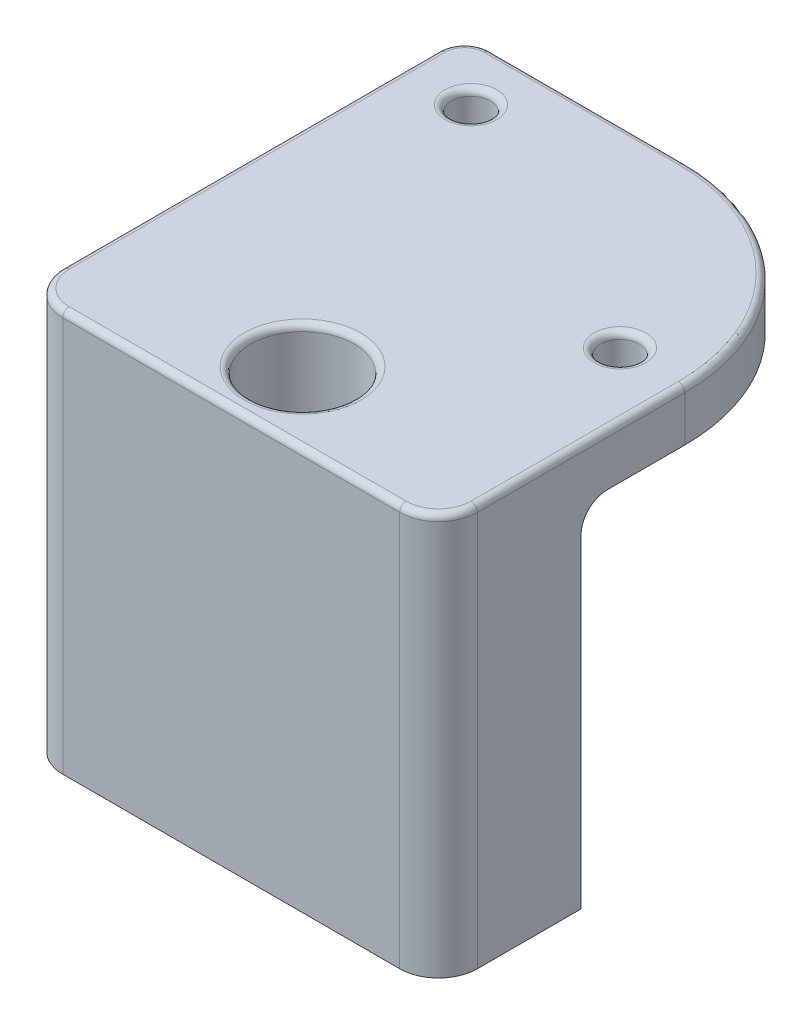
SolidWorks part; units mm, degrees
ref_plane "Спереди" through (0, 0, 0) normal (0, 0, 1) x (1, 0, 0)
ref_plane "Сверху" through (0, 0, 0) normal (0, 1, 0) x (1, 0, 0)
ref_plane "Справа" through (0, 0, 0) normal (1, 0, 0) x (0, 0, -1)
sketch "Эскиз1" plane through (0, 0, 0) normal (0, 1, 0) x (1, 0, 0)
  line L0 (0, 5.5) -> (32, 5.5) construction
  line L1 (0, 0) -> (32, 0)
  line L2 (0, 0) -> (0, 11)
  line L3 (0, 11) -> (32, 11)
  line L4 (32, 0) -> (32, 11)
  line L5 (16, 11) -> (16, 0) construction
  circle A0 centre (16, 5.5) radius 1.6
  dimension "D3" = 3.2
  dimension "D1" = 11
  dimension "D2" = 32
extrude "Бобышка-Вытянуть1" add sketch "Эскиз1" along normal blind 27
sketch "Эскиз2" plane through (0, 27, 0) normal (0, 1, 0) x (1, 0, 0)
  line L0 (32, 0) -> (32, 11) construction
  line L1 (0, 0) -> (0, 34)
  line L2 (0, 34) -> (17, 34)
  line L4 (32, 0) -> (32, 19)
  line L5 (32, 0) -> (0, 0)
  circle A0 centre (5, 29.5) radius 1.5
  circle A1 centre (27, 19) radius 1.5
  arc A2 (32, 19) -> (17, 34) centre (17, 19) ccw
  point P15 (32, 34)
  point P18 (0, 34)
  dimension "D6" = 3
  dimension "D7" = 3
  dimension "D8" = 5
  dimension "D10" = 15
  dimension "D5" = 29.5
  dimension "D11" = 19
  dimension "D2" = 32
  dimension "D3" = 34
  dimension "D4" = 0
extrude "Бобышка-Вытянуть2" add sketch "Эскиз2" along normal blind 4
fillet "Скругление3" radius 3 1 edges at (32, 15.5, 0) tangent propagation no
fillet "Скругление4" radius 3 1 edges at (0, 15.5, 0) tangent propagation no
sketch "Эскиз3" plane through (0, 27, 0) normal (0, -1, 0) x (1, 0, 0)
  circle A0 centre (16, -5.5) radius 4
  dimension "D1" = 8
extrude "Вырез-Вытянуть1" cut sketch "Эскиз3" against normal blind 15 from offset 10
fillet "Скругление5" radius 2 1 edges at (16, 27, -11)
sketch "Эскиз4" plane through (0, 27, 0) normal (0, -1, 0) x (1, 0, 0)
  circle A0 centre (5, -29.5) radius 3
  circle A1 centre (5, -29.5) radius 1.5
  dimension "D1" = 6
extrude "Бобышка-Вытянуть3" add sketch "Эскиз4" along normal blind 9.5
fillet "Скругление6" radius 2 1 edges at (0, 29, -34)
fillet "Скругление7" radius 0.5 11 edges at (27, 31, -17.5) (27.6066, 31, -29.6066) (32, 31, -11) (0, 31, -17.5) (0.5858, 31, -33.4142) (9.5, 31, -34) (5, 31, -28) (31.1213, 31, -0.8787) (16, 31, 0) (0.8787, 31, -0.8787) (16, 31, -1.5)
